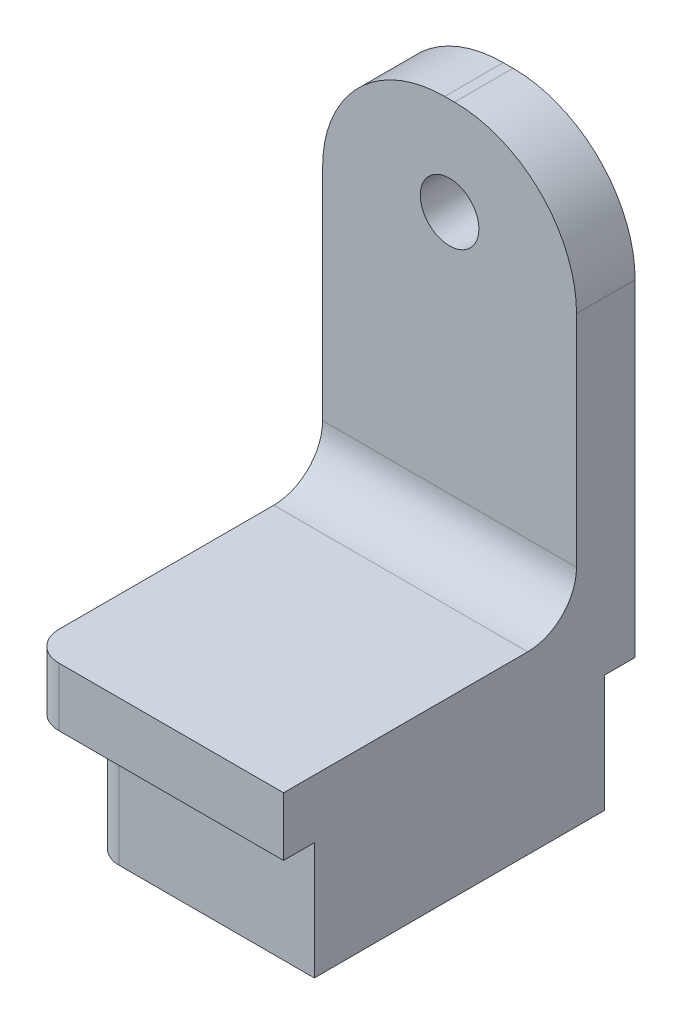
SolidWorks part; units mm, degrees
ref_plane "Front Plane" through (0, 0, 0) normal (0, 0, 1) x (1, 0, 0)
ref_plane "Top Plane" through (0, 0, 0) normal (0, 1, 0) x (1, 0, 0)
ref_plane "Right Plane" through (0, 0, 0) normal (1, 0, 0) x (0, 0, -1)
sketch "Sketch1" plane through (0, -44, 0) normal (0, 1, 0) x (1, 0, 0)
  line L0 (50.2641, 25) -> (50.2641, 28) construction
  line L1 (50.2641, -8) -> (50.2641, 28)
  line L2 (50.2641, -8) -> (27.2641, -8) construction
  line L3 (50.2641, -8) -> (27.2641, -8)
  line L4 (24.2641, -5) -> (24.2641, 25)
  line L5 (27.2641, 28) -> (50.2641, 28)
  arc A0 (27.2641, 28) -> (24.2641, 25) centre (27.2641, 25) ccw construction
  arc A1 (24.2641, -5) -> (27.2641, -8) centre (27.2641, -5) ccw construction
  arc A2 (27.2641, 28) -> (24.2641, 25) centre (27.2641, 25) ccw
  arc A3 (24.2641, -5) -> (27.2641, -8) centre (27.2641, -5) ccw
extrude "Boss-Extrude1" add sketch "Sketch1" along normal blind 6
sketch "Sketch2" plane through (0, -38, 0) normal (0, 1, 0) x (1, 0, 0)
  line L0 (24.2641, 25) -> (24.2641, -5) construction
  line L1 (50.2641, 28) -> (24.2641, 28)
  line L2 (50.2641, 28) -> (50.2641, 22)
  line L3 (50.2641, 22) -> (24.2641, 22)
  line L4 (24.2641, 28) -> (24.2641, 22)
  dimension "D1" = 6
extrude "Boss-Extrude2" add sketch "Sketch2" along normal blind 40
fillet "Fillet1" radius 12.5 2 edges at (24.2641, 2, -25) (50.2641, 2, -25)
sketch "Sketch3" plane through (0, 0, -22) normal (0, 0, 1) x (1, 0, 0)
  circle A0 centre (37.2641, -8) radius 3
extrude "Cut-Extrude1" cut sketch "Sketch3" against normal through all
sketch "Sketch4" plane through (0, -44, 0) normal (0, -1, 0) x (1, 0, 0)
  line L3 (50.2641, 4.85) -> (50.2641, -24.85)
  line L6 (50.2641, -24.85) -> (30.2641, -24.85)
  line L7 (27.4141, 2) -> (27.4141, -22)
  line L8 (30.2641, 4.85) -> (50.2641, 4.85)
  arc A4 (27.4141, -22) -> (30.2641, -24.85) centre (30.2641, -22) ccw
  arc A5 (30.2641, 4.85) -> (27.4141, 2) centre (30.2641, 2) ccw
extrude "Boss-Extrude3" add sketch "Sketch4" along normal blind 12
fillet "Fillet2" radius 5 1 edges at (37.2641, -38, -22)
